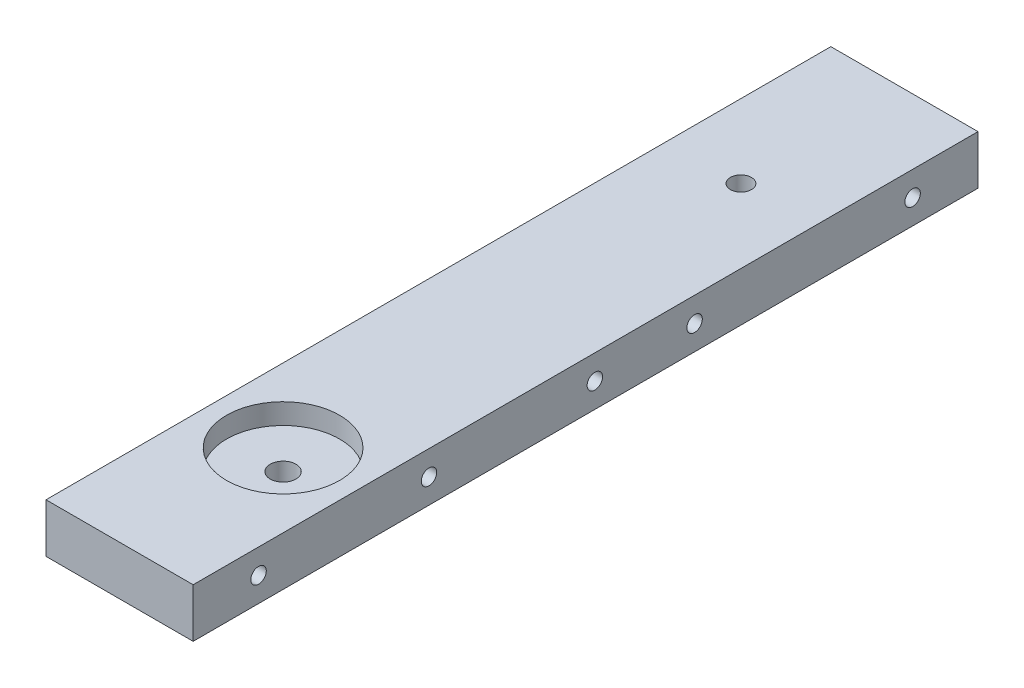
SolidWorks part; units mm, degrees
ref_plane "Front Plane" through (0, 0, 0) normal (0, 0, 1) x (1, 0, 0)
ref_plane "Top Plane" through (0, 0, 0) normal (0, 1, 0) x (1, 0, 0)
ref_plane "Right Plane" through (0, 0, 0) normal (1, 0, 0) x (0, 0, -1)
sketch "Sketch2" plane through (0, 0, 0) normal (0, 1, 0) x (1, 0, 0)
  line L0 (0, 0) -> (0, 152.4)
  line L1 (0, 152.4) -> (28.575, 152.4)
  line L2 (28.575, 152.4) -> (28.575, 0)
  line L3 (28.575, 0) -> (0, 0)
  dimension "D1" = 152.4
  dimension "D2" = 28.575
extrude "Boss-Extrude1" add sketch "Sketch2" along normal blind 9.525
sketch "Sketch3" plane through (0, 0, 0) normal (-1, 0, 0) x (0, 0, 1)
  line L3 (-152.4, 9.525) -> (0, 9.525) construction
  line L4 (-152.4, 9.525) -> (-152.4, 0) construction
  point P6 (-139.7, 4.7625)
  point P14 (-139.7, 4.7625)
  dimension "D1" = 4.7625
  dimension "D2" = 12.7
sketch "Sketch8" plane through (0, 0, 0) normal (-1, 0, 0) x (0, 0, 1)
  point P0 (-139.7, 4.7625)
hole_wizard "Ø3.0mm Dowel Hole1" positions "Sketch8" profile "Sketch9" hole size "Ø3.0" standard "ANSI Metric" end condition through all
sketch "Sketch9" plane through (0, 4.7625, -139.7) normal (0, 1, 0) x (0, 0, 1)
  line L0 (0, 0) -> (0, 28.575)
  line L1 (0, 28.575) -> (1.5, 28.575)
  line L2 (1.5, 28.575) -> (1.5, 0)
  line L5 (1.5, 0) -> (0, 0)
  line L11 (0, -6.35) -> (0, 107.95) construction
  dimension "Thru Hole Dia." = 3
  dimension "Thru Hole Depth" = 28.575
pattern_linear "LPattern1" count 4 spacing 42.3333 along (0, 0, 1) skipping (2, 0) of "Ø3.0mm Dowel Hole1"
sketch "Sketch12" plane through (0, 9.525, 0) normal (0, 1, 0) x (1, 0, 0)
  line L0 (28.575, 0) -> (28.575, 152.4) construction
  line L2 (0, 0) -> (28.575, 0) construction
  circle A1 centre (14.2875, 31.75) radius 10.975
  circle A2 centre (14.2875, 120.65) radius 2.05
  point P0 (14.2875, 120.65)
  point P1 (14.2875, 76.2)
  point P2 (14.2875, 31.75)
  dimension "D8" = 4.1
  dimension "D9" = 21.95
  dimension "D1" = 14.2875
  dimension "D2" = 14.2875
  dimension "D3" = 14.2875
  dimension "D4" = 76.2
  dimension "D5" = 44.45
  dimension "D6" = 44.45
sketch "Sketch13" plane through (0, 0, 0) normal (-1, 0, 0) x (0, 0, 1)
  line L2 (0, 9.525) -> (0, 0) construction
  line L3 (-152.4, 9.525) -> (0, 9.525) construction
  point P5 (-78, 4.7625)
  point P11 (-45.79, 4.7625)
  dimension "D1" = 78
  dimension "D2" = 4.7625
  dimension "D3" = 32.21
hole_wizard "Ø3.0mm Dowel Hole2" positions "Sketch13" profile "Sketch14" hole size "Ø3.0" standard "ANSI Metric" end condition through all
sketch "Sketch14" plane through (0, 4.7625, -78) normal (0, 1, 0) x (0, 0, 1)
  line L0 (0, 0) -> (0, 28.575)
  line L1 (0, 28.575) -> (1.5, 28.575)
  line L2 (1.5, 28.575) -> (1.5, 0)
  line L5 (1.5, 0) -> (0, 0)
  line L11 (0, -6.35) -> (0, 107.95) construction
  dimension "Thru Hole Dia." = 3
  dimension "Thru Hole Depth" = 28.575
extrude "Cut-Extrude1" cut sketch "Sketch12" against normal through all contours A2
extrude "Cut-Extrude2" cut sketch "Sketch12<4>" against normal blind 4 contours A1
sketch "Sketch12<4>" plane through (0, 9.525, 0) normal (0, 1, 0) x (1, 0, 0) same geometry as "Sketch12"
sketch "Sketch15" plane through (0, 5.525, 0) normal (0, 1, 0) x (1, 0, 0)
  circle A0 centre (14.2875, 31.75) radius 2.5
  dimension "D1" = 5
extrude "Cut-Extrude3" cut sketch "Sketch15" against normal through all
